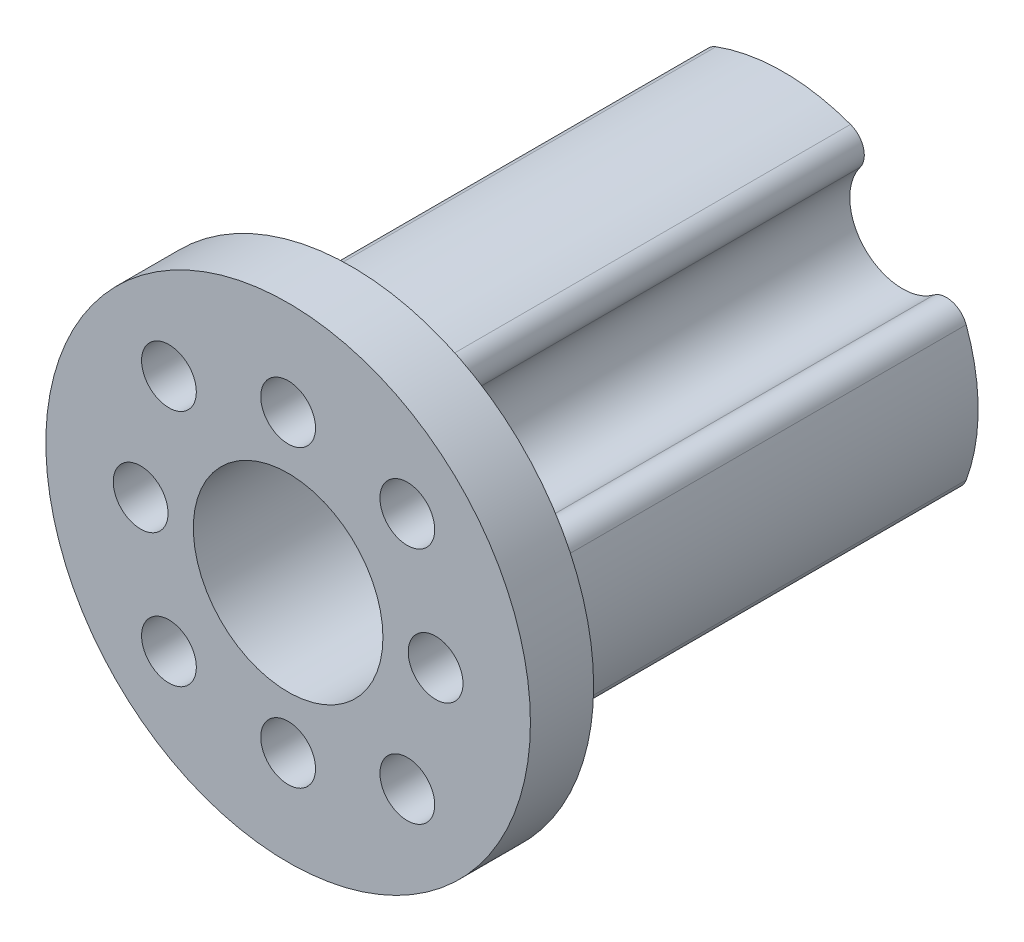
SolidWorks part; units mm, degrees
ref_plane "Plan de face" through (0, 0, 0) normal (0, 0, 1) x (1, 0, 0)
ref_plane "Plan de dessus" through (0, 0, 0) normal (0, 1, 0) x (1, 0, 0)
ref_plane "Plan de droite" through (0, 0, 0) normal (1, 0, 0) x (0, 0, -1)
sketch "Esquisse1" plane through (0, 0, 0) normal (0, 0, 1) x (1, 0, 0)
  circle A0 centre (0, 0) radius 9.25
  dimension "D1" = 18.5
extrude "Boss.-Extru.1" add sketch "Esquisse1" along normal blind 23.5
sketch "Esquisse2" plane through (0, 0, 23.5) normal (0, 0, 1) x (1, 0, 0)
  line L0 (0, 0) -> (7, 0) construction
  circle A0 centre (7, 0) radius 1.3
  circle A1 centre (0, -7) radius 1.3
  circle A2 centre (-7, 0) radius 1.3
  circle A3 centre (0, 7) radius 1.3
  point P13 (0, 0)
  dimension "D1" = 2.6
  dimension "D2" = 7
  dimension "D3" = 4
extrude "Enlèv. mat.-Extru.1" cut sketch "Esquisse2" against normal through all both and the other way through all
sketch "Esquisse3" plane through (0, 0, 23.5) normal (0, 0, 1) x (1, 0, 0)
  circle A1 centre (0, 0) radius 4.5
  dimension "D1" = 9
extrude "Enlèv. mat.-Extru.2" cut sketch "Esquisse3" against normal through all both and the other way through all
sketch "Esquisse4" plane through (0, 0, 23.5) normal (0, 0, 1) x (1, 0, 0)
  circle A0 centre (0, 0) radius 9.25
  circle A1 centre (0, 0) radius 11.5
  circle A2 centre (0, 0) radius 9.25 construction
  dimension "D1" = 23
extrude "Boss.-Extru.2" add sketch "Esquisse4" against normal blind 3
sketch "Esquisse5" plane through (0, 0, 23.5) normal (0, 0, 1) x (1, 0, 0)
  line L0 (5.6569, 5.6569) -> (0, 0) construction
  line L1 (0, 0) -> (2.5725, 0) construction
  circle A0 centre (5.6569, 5.6569) radius 2.5
  circle A1 centre (5.6569, -5.6569) radius 2.5
  circle A2 centre (-5.6569, -5.6569) radius 2.5
  circle A3 centre (-5.6569, 5.6569) radius 2.5
  point P13 (0, 0)
  point P14 (0, 0)
  dimension "D3" = 5
  dimension "D1" = 45
  dimension "D2" = 8
  dimension "D4" = 4
extrude "Enlèv. mat.-Extru.3" cut sketch "Esquisse5" against normal through all both and the other way through all
sketch "Esquisse6" plane through (0, 0, 23.5) normal (0, 0, 1) x (1, 0, 0)
  circle A0 centre (-5.6569, 5.6569) radius 2.5
  circle A1 centre (-5.6569, 5.6569) radius 1.3
  circle A2 centre (-5.6569, 5.6569) radius 2.5 construction
  circle A3 centre (5.6569, 5.6569) radius 2.5
  circle A4 centre (5.6569, 5.6569) radius 1.3
  circle A5 centre (5.6569, -5.6569) radius 2.5
  circle A6 centre (5.6569, -5.6569) radius 1.3
  circle A7 centre (-5.6569, -5.6569) radius 2.5
  circle A8 centre (-5.6569, -5.6569) radius 1.3
  point P18 (0, 0)
  dimension "D1" = 2.6
  dimension "D2" = 4
extrude "Boss.-Extru.3" add sketch "Esquisse6" against normal up to vertex (3 mm away) up to point (-7.9667, 4.7005, 20.5)
fillet "Congé1" radius 1 8 edges at (7.9667, -4.7005, 10.25) (4.7005, -7.9667, 10.25) (-4.7005, -7.9667, 10.25) (-7.9667, -4.7005, 10.25) (-7.9667, 4.7005, 10.25) (-4.7005, 7.9667, 10.25) (4.7005, 7.9667, 10.25) (7.9667, 4.7005, 10.25)
